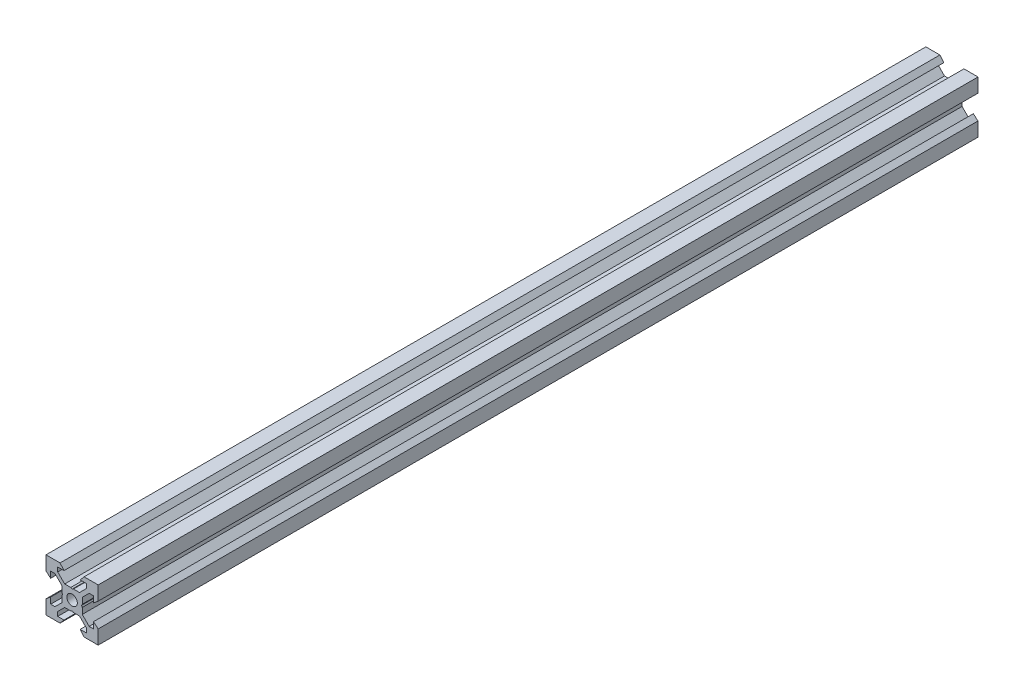
SolidWorks part; units mm, degrees
ref_plane "Front Plane" through (0, 0, 0) normal (0, 0, 1) x (1, 0, 0)
ref_plane "Top Plane" through (0, 0, 0) normal (0, 1, 0) x (1, 0, 0)
ref_plane "Right Plane" through (0, 0, 0) normal (1, 0, 0) x (0, 0, -1)
sketch "Sketch1" plane through (0, 0, 0) normal (0, 0, 1) x (1, 0, 0)
  line L0 (10, 10) -> (4.6104, 10) construction
  line L1 (10, 10) -> (10, 4.6104) construction
  line L2 (10, -10) -> (10, -4.6104) construction
  line L3 (10, -10) -> (4.6104, -10) construction
  line L4 (10, 10) -> (10, 4.6104)
  line L5 (6.5607, 5.5) -> (8.2, 5.5)
  line L6 (5.5, 8.2) -> (5.5, 6.5607)
  line L7 (10, 10) -> (4.6104, 10)
  line L8 (10, 10) -> (10, 4.6104)
  line L9 (6.5607, 5.5) -> (3.9, 2.8393)
  line L10 (5.5, 6.5607) -> (2.8393, 3.9)
  line L11 (10, 4.6104) -> (8.2, 3.1)
  line L12 (4.6104, 10) -> (3.1, 8.2)
  line L13 (8.2, 3.1) -> (8.2, 5.5)
  line L14 (3.1, 8.2) -> (5.5, 8.2)
  line L15 (-6.5607, 5.5) -> (-8.2, 5.5)
  line L16 (6.5607, -5.5) -> (8.2, -5.5)
  line L17 (3.1, -8.2) -> (5.5, -8.2)
  line L18 (8.2, -3.1) -> (8.2, -5.5)
  line L19 (4.6104, -10) -> (3.1, -8.2)
  line L20 (10, -4.6104) -> (8.2, -3.1)
  line L21 (0.5196, -3.9) -> (0, -3.6)
  line L22 (0.5196, 3.9) -> (0, 3.6)
  line L23 (3.6, 0) -> (3.9, -0.5196)
  line L24 (3.9, 0.5196) -> (3.6, 0)
  line L25 (3.9, 0.5196) -> (3.9, 2.8393)
  line L26 (2.8393, 3.9) -> (0.5196, 3.9)
  line L27 (3.9, -2.8393) -> (3.9, -0.5196)
  line L28 (2.8393, -3.9) -> (0.5196, -3.9)
  line L29 (5.5, -6.5607) -> (2.8393, -3.9)
  line L30 (6.5607, -5.5) -> (3.9, -2.8393)
  line L31 (10, -10) -> (10, -4.6104)
  line L32 (10, -10) -> (4.6104, -10)
  line L33 (5.5, -8.2) -> (5.5, -6.5607)
  line L34 (-6.5607, -5.5) -> (-8.2, -5.5)
  line L35 (10, -10) -> (10, -4.6104)
  line L36 (0, 0) -> (0, 8.2) construction
  line L37 (-10, -10) -> (-4.6104, -10) construction
  line L38 (-10, -10) -> (-10, -4.6104) construction
  line L39 (-10, 10) -> (-10, 4.6104) construction
  line L40 (-10, 10) -> (-4.6104, 10) construction
  line L41 (-10, -10) -> (-10, -4.6104)
  line L43 (-5.5, -8.2) -> (-5.5, -6.5607)
  line L44 (-10, -10) -> (-4.6104, -10)
  line L45 (-10, -10) -> (-10, -4.6104)
  line L46 (-6.5607, -5.5) -> (-3.9, -2.8393)
  line L47 (-5.5, -6.5607) -> (-2.8393, -3.9)
  line L48 (-2.8393, -3.9) -> (-0.5196, -3.9)
  line L49 (-3.9, -2.8393) -> (-3.9, -0.5196)
  line L50 (-2.8393, 3.9) -> (-0.5196, 3.9)
  line L51 (-3.9, 0.5196) -> (-3.9, 2.8393)
  line L52 (-3.9, 0.5196) -> (-3.6, 0)
  line L53 (-3.6, 0) -> (-3.9, -0.5196)
  line L54 (-0.5196, 3.9) -> (0, 3.6)
  line L55 (-0.5196, -3.9) -> (0, -3.6)
  line L56 (-10, -4.6104) -> (-8.2, -3.1)
  line L57 (-4.6104, -10) -> (-3.1, -8.2)
  line L58 (-8.2, -3.1) -> (-8.2, -5.5)
  line L59 (-3.1, -8.2) -> (-5.5, -8.2)
  line L60 (-10, -10) -> (10, -10) construction
  line L61 (-10, -10) -> (-10, 10) construction
  line L62 (-3.1, 8.2) -> (-5.5, 8.2)
  line L63 (-8.2, 3.1) -> (-8.2, 5.5)
  line L64 (-4.6104, 10) -> (-3.1, 8.2)
  line L65 (-10, 4.6104) -> (-8.2, 3.1)
  line L66 (-5.5, 6.5607) -> (-2.8393, 3.9)
  line L67 (-6.5607, 5.5) -> (-3.9, 2.8393)
  line L68 (-10, 10) -> (-10, 4.6104)
  line L69 (-10, 10) -> (-4.6104, 10)
  line L70 (-5.5, 8.2) -> (-5.5, 6.5607)
  line L71 (-10, 10) -> (10, 10) construction
  line L72 (-10, 10) -> (-10, 4.6104)
  line L73 (10, -10) -> (10, 10) construction
  line L74 (-10, -10) -> (10, 10) construction
  line L75 (-10, 10) -> (10, -10) construction
  circle A0 centre (0, 0) radius 2
  dimension "D7" = 4
  dimension "D1" = 20
  dimension "D2" = 5.3896
  dimension "D3" = 4.5
  dimension "D4" = 50
  dimension "D5" = 1.8
  dimension "D6" = 1.5104
  dimension "D8" = 5.5
  dimension "D9" = 120
  dimension "D10" = 0.3
  dimension "D11" = 2.3197
  dimension "D12" = 7.8
  dimension "D13" = 7.8
  dimension "D14" = 1.5
  dimension "D15" = 2.6607
extrude "Boss-Extrude1" add sketch "Sketch1" along normal mid plane 337.33 contours L70 L62 L64 L69 L68 L65 L63 L15 L67 L51 L52 L53 L49 L46 L34 L58 L56 L41 L44 L57 L59 L43 L47 L48 L55 L21 L28 L29 L33 L17 L19 L32 L31 L20 L18 L16 L30 L27 L23 L24 L25 L9 L5 L13 L11 L4 L7 L12 L14 L6 L10 region at (9.7172, 7.3052, 0)
